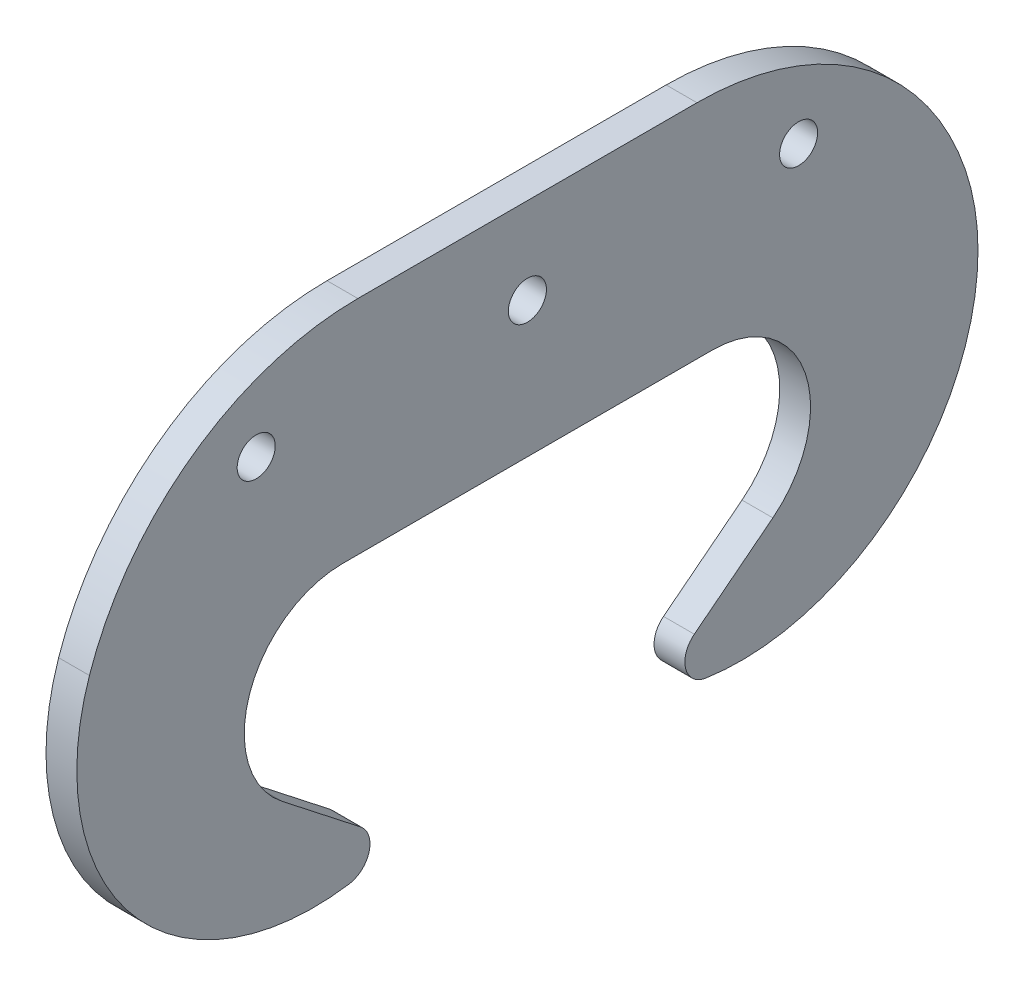
SolidWorks part; units mm, degrees
note: The reader was unsure of these and kept them because the rebuilt part matched: shared geometry of "Sketch9<2>".
other "Static 1"
material "AISI 4130 Steel, normalized at 870C"
ref_plane "Front Plane" through (0, 0, 0) normal (0, 0, 1) x (1, 0, 0)
ref_plane "Top Plane" through (0, 0, 0) normal (0, 1, 0) x (1, 0, 0)
ref_plane "Right Plane" through (0, 0, 0) normal (1, 0, 0) x (0, 0, -1)
sketch "Sketch1" plane through (0, 0, 0) normal (1, 0, 0) x (0, 0, -1)
  line L0 (63.5, 0) -> (-63.5, 0) construction
  line L1 (63.5, -84.1375) -> (-63.5, -84.1375)
  line L2 (63.5, 84.1375) -> (-63.5, 84.1375)
  line L3 (31.75, -84.1375) -> (-31.75, -84.1375)
  line L6 (-68.2625, -4.7625) -> (68.2625, -4.7625)
  line L7 (-68.2625, -4.7625) -> (-68.2625, -74.6125)
  line L8 (-68.2625, -74.6125) -> (68.2625, -74.6125)
  line L9 (68.2625, -4.7625) -> (68.2625, -74.6125)
  line L10 (-68.2625, -4.7625) -> (68.2625, -74.6125) construction
  line L11 (-68.2625, -74.6125) -> (68.2625, -4.7625) construction
  line L12 (-31.75, -74.6125) -> (-34.925, -84.1375)
  line L13 (34.925, -72.1277) -> (68.2625, -46.0375)
  line L14 (-34.925, -72.1277) -> (-31.75, -74.6125)
  line L15 (-34.925, -72.1277) -> (-68.2625, -46.0375)
  line L16 (31.75, -74.6125) -> (34.925, -84.1375)
  line L17 (31.75, -74.6125) -> (34.925, -72.1277)
  line L18 (-34.925, -72.1277) -> (-34.925, -74.6125) construction
  line L19 (-34.925, -74.6125) -> (-34.925, -84.1375) construction
  line L20 (34.925, -72.1277) -> (34.925, -74.6125) construction
  line L21 (34.925, -74.6125) -> (34.925, -84.1375) construction
  arc A0 (63.5, -84.1375) -> (63.5, 84.1375) centre (63.5, 0) ccw
  arc A1 (-63.5, 84.1375) -> (-63.5, -84.1375) centre (-63.5, 0) ccw
  point P2 (0, 0)
  point P8 (0, -39.6875)
  point P18 (0, -84.1375)
  dimension "D1" = 84.1375
  dimension "D6" = 3.175
  dimension "D7" = 28.575
  dimension "D2" = 127
  dimension "D3" = 136.525
  dimension "D4" = 69.85
  dimension "D5" = 88.9
  dimension "D8" = 69.85
extrude "Boss-Extrude1" add sketch "Sketch1" along normal blind 7.9375
fillet "Fillet1" radius 25.4 2 edges at (3.9688, -46.0375, 68.2625) (3.9688, -46.0375, -68.2625)
fillet "Fillet2" radius 16.51 2 edges at (3.9688, -4.7625, 68.2625) (3.9688, -4.7625, -68.2625)
hole_wizard "3/8 Clearance Hole1" positions "3DSketch1" profile "Sketch5" hole size "3/8" standard "ANSI Inch" end condition through all
sketch3d "3DSketch1"
  line L0 (7.9375, 30.1625, 69.85) -> (7.9375, 30.1625, -69.85) construction
  line L4 (7.9375, 84.1375, -63.5) -> (7.9375, 84.1375, 63.5) construction
  line L5 (0, 0, 0) -> (7.9375, 30.1625, 0) construction
  point P0 (7.9375, 30.1625, 69.85)
  point P2 (7.9375, 30.1625, 0)
  point P4 (7.9375, 30.1625, -69.85)
  point P11 (7.9375, 30.1625, 0)
  dimension "D2" = 53.975
  dimension "D3" = 139.7
sketch "Sketch5" plane through (7.9375, 30.1625, 69.85) normal (0, 1, 0) x (0, 0, -1)
  line L0 (0, 0) -> (0, 7.9375)
  line L1 (0, 7.9375) -> (4.9022, 7.9375)
  line L2 (4.9022, 7.9375) -> (4.9022, 0)
  line L5 (4.9022, 0) -> (0, 0)
  line L11 (0, -6.35) -> (0, 107.95) construction
  dimension "Thru Hole Dia." = 9.8044
  dimension "Thru Hole Depth" = 7.9375
fillet "Fillet3" [suppressed] radius 3.175
sketch "Sketch8" plane through (7.9375, 0, 0) normal (1, 0, 0) x (0, 0, -1)
  line L0 (-69.85, 30.1625) -> (0, 30.1625) construction
  line L1 (-34.925, 14.2875) -> (34.925, 14.2875) construction
  line L2 (0, 14.2875) -> (0, 0) construction
  line L3 (-51.7525, -4.7625) -> (51.7525, -4.7625) construction
  line L4 (-31.75, 24.9368) -> (-11.3393, 18.8515)
  line L5 (-11.3393, 9.7235) -> (-31.75, 3.6382)
  line L6 (11.3393, 18.8515) -> (31.75, 24.9368)
  line L7 (31.75, 3.6382) -> (11.3393, 9.7235)
  circle A0 centre (-34.925, 14.2875) radius 11.1125
  circle A1 centre (34.925, 14.2875) radius 11.1125
  circle A2 centre (-12.7, 14.2875) radius 4.7625
  circle A3 centre (12.7, 14.2875) radius 4.7625
  dimension "D1" = 22.225
  dimension "D2" = 69.85
  dimension "D6" = 9.525
  dimension "D3" = 19.05
  dimension "D4" = 25.4
  dimension "D5" = 12.7
extrude "Cut-Extrude2" [suppressed] cut sketch "Sketch8" against normal up to next contours A0 | A2 L4 A0 L5 | A2 | A3 | A3 L7 A1 L6 | A1
sketch "Sketch9" plane through (7.9375, 0, 0) normal (1, 0, 0) x (0, 0, -1)
  line L0 (-47.625, -4.7625) -> (47.625, -4.7625)
  line L1 (-58.5167, -53.6646) -> (-31.75, -74.6125) construction
  line L2 (-63.2174, -49.9858) -> (-31.75, -74.6125)
  line L3 (-51.7525, -4.7625) -> (51.7525, -4.7625) construction
  line L4 (0, 0) -> (0, -49.6898) construction
  line L5 (63.2174, -49.9858) -> (31.75, -74.6125)
  line L6 (-58.5167, -53.6646) -> (-31.75, -74.6125) construction
  arc A2 (-63.2174, -49.9858) -> (-47.625, -4.7625) centre (-47.625, -30.0622) cw
  arc A3 (63.2174, -49.9858) -> (47.625, -4.7625) centre (47.625, -30.0622) ccw
  dimension "D3" = 47.625
extrude "Extrude-Thin1" add sketch "Sketch9" against normal up to surface (7.9375 mm away) thin up to face at (0, 30.1625, 64.9478) thin type one direction wall 5.08
extrude "Cut-Extrude-Thin2" cut sketch "Sketch9<2>" against normal up to next thin
sketch "Sketch9<2>" plane through (7.9375, 0, 0) normal (1, 0, 0) x (0, 0, -1) same geometry as "Sketch9"
sketch "Sketch7" plane through (7.9375, 0, 0) normal (1, 0, 0) x (0, 0, -1)
  line L0 (43.6683, 52.3875) -> (-43.6683, 52.3875)
  line L1 (-47.625, -4.7625) -> (47.625, -4.7625) construction
  line L2 (44.45, -76.8519) -> (31.75, -74.6125)
  line L3 (0, 0) -> (0, 52.3875) construction
  line L4 (-44.45, -76.8519) -> (-31.75, -74.6125)
  circle A0 centre (69.85, 30.1625) radius 15.875 construction
  arc A1 (43.6683, 52.3875) -> (112.8056, 2.8716) centre (43.6683, -20.6375) cw
  arc A2 (112.8056, 2.8716) -> (44.45, -76.8519) centre (55.0442, -16.7693) cw
  arc A3 (-112.8056, 2.8716) -> (-44.45, -76.8519) centre (-55.0442, -16.7693) ccw
  arc A4 (-43.6683, 52.3875) -> (-112.8056, 2.8716) centre (-43.6683, -20.6375) ccw
  point P3 (0, 55.5625)
  dimension "D1" = 57.15
  dimension "D2" = 31.75
  dimension "D6" = 12.7
  dimension "D3" = 73.025
  dimension "D7" = 100
extrude "Cut-Extrude-Thin1" cut sketch "Sketch7" against normal blind 152.4 and the other way through all thin contours L4 A3 A4 L0 A1 A2 L2
fillet "Fillet4" radius 6.35 2 edges at (3.9688, -74.6125, 31.75) (3.9688, -74.6125, -31.75)
